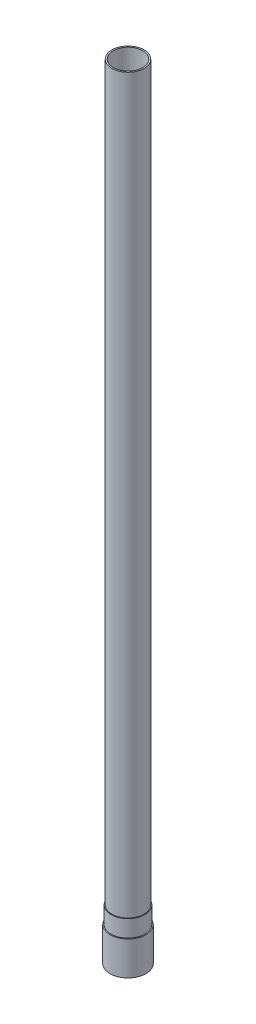
SolidWorks part; units mm, degrees
ref_plane "Front Plane" through (0, 0, 0) normal (0, 0, 1) x (1, 0, 0)
ref_plane "Top Plane" through (0, 0, 0) normal (0, 1, 0) x (1, 0, 0)
ref_plane "Right Plane" through (0, 0, 0) normal (1, 0, 0) x (0, 0, -1)
sketch "Sketch1" plane through (0, 0, 0) normal (0, 1, 0) x (1, 0, 0)
  circle A0 centre (0, 0) radius 15
  circle A1 centre (0, 0) radius 13.462
  circle A2 centre (0, 0) radius 15.875
  dimension "D1" = 30
  dimension "D2" = 31.75
  dimension "D3" = 2.413
extrude "Boss-Extrude1" add sketch "Sketch1" along normal blind 15 contours A0 A1 region at (-14.5757, 0, 0)
sketch "Sketch4" plane through (0, 15, 0) normal (0, 1, 0) x (1, 0, 0)
  circle A0 centre (0, 0) radius 14.2875
  circle A2 centre (0, 0) radius 13.0429
  circle M3 centre (0, 0) radius 13.462
  dimension "D1" = 28.575
  dimension "D2" = 1.2446
extrude "Boss-Extrude5" add sketch "Sketch4" along normal blind 650 contours A2 M3 | A0 M3 region at (-13.8834, 15, 0) region at (-13.0812, 15, 0)
extrude "Boss-Extrude6" add sketch "Sketch1<4>" against normal blind 30 contours A2 A0 | A0 A1 region at (-14.5757, 0, 0) region at (-15.426, 0, 0)
sketch "Sketch1<4>" plane through (0, 0, 0) normal (0, 1, 0) x (1, 0, 0) same geometry as "Sketch1"
equation "\"bottomheight\"= 15"
equation "\"D1@Boss-Extrude1\"=\"bottomheight\""
equation "\"topheight\"= 650"
equation "\"D1@Boss-Extrude5\"=\"topheight\""
equation "\"spacerheight\"=30"
equation "\"D1@Boss-Extrude6\"=\"spacerheight\""
